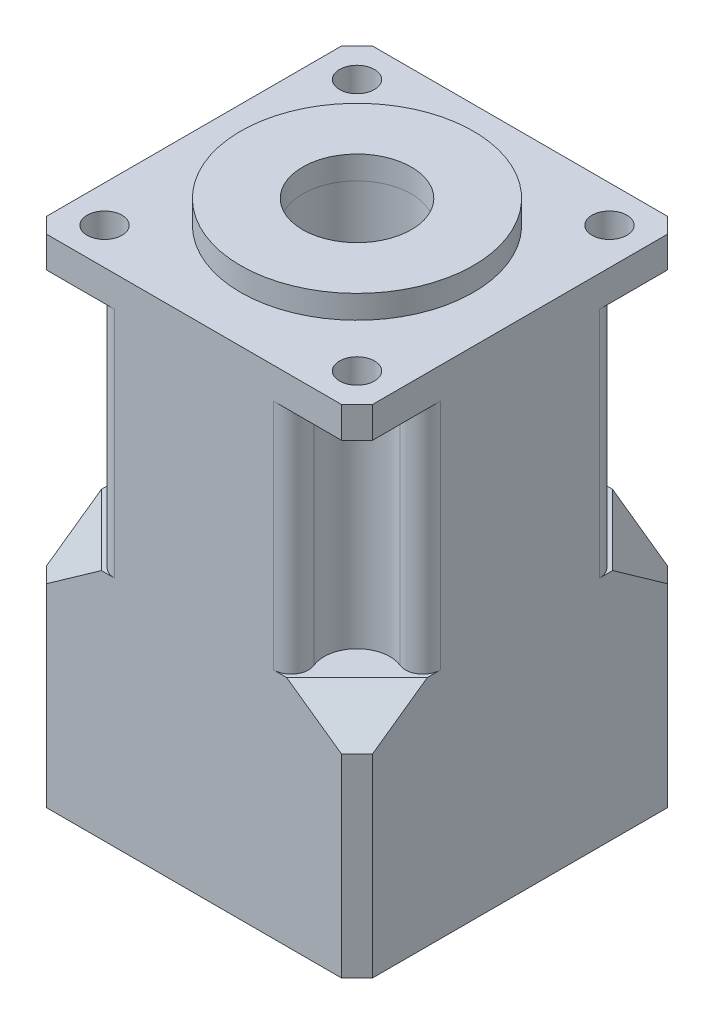
SolidWorks part; units mm, degrees
ref_plane "Front Plane" through (0, 0, 0) normal (0, 0, 1) x (1, 0, 0)
ref_plane "Top Plane" through (0, 0, 0) normal (0, 1, 0) x (1, 0, 0)
ref_plane "Right Plane" through (0, 0, 0) normal (1, 0, 0) x (0, 0, -1)
sketch "Sketch1" plane through (0, 0, 0) normal (0, 1, 0) x (1, 0, 0)
  line L0 (0, 0) -> (-23, 0) construction
  line L1 (-19, 21) -> (19, 21)
  line L2 (-21, 19) -> (-21, -19)
  line L3 (-19, -21) -> (19, -21)
  line L4 (21, 19) -> (21, -19)
  line L5 (-21, 21) -> (21, -21) construction
  line L6 (-21, -21) -> (21, 21) construction
  line L7 (-19, 21) -> (-21, 19)
  line L8 (19, 21) -> (21, 19)
  line L9 (-21, -19) -> (-19, -21)
  line L10 (19, -21) -> (21, -19)
  circle A0 centre (0, 0) radius 23 construction
  circle A1 centre (-16.2635, 16.2635) radius 2.25
  circle A3 centre (16.2635, 16.2635) radius 2.25
  circle A4 centre (16.2635, -16.2635) radius 2.25
  circle A5 centre (-16.2635, -16.2635) radius 2.25
  circle A6 centre (0, 0) radius 15
  circle A7 centre (0, 0) radius 7
  point P0 (0, 0)
  dimension "D3" = 23
  dimension "D1" = 42
  dimension "D2" = 42
extrude "Boss-Extrude1" add sketch "Sketch1" along normal blind 26 contours A7 region at (0, 0, 0)
extrude "Boss-Extrude2" add sketch "Sketch1<3>" along normal blind 3 contours A6 A7 region at (-14.5757, 0, 0)
sketch "Sketch1<3>" plane through (0, 0, 0) normal (0, 1, 0) x (1, 0, 0) same geometry as "Sketch1"
extrude "Boss-Extrude3" add sketch "Sketch1<4>" against normal blind 4 separate body contours A6 A7 | L3 L10 L4 L8 L1 L7 L2 L9 A6 A4 A3 A1 A5 | A7 region at (0, 0, -20.406) region at (-14.5757, 0, 0) region at (0, 0, 0)
sketch "Sketch1<4>" plane through (0, 0, 0) normal (0, 1, 0) x (1, 0, 0) same geometry as "Sketch1"
sketch "Sketch3" plane through (0, -4, 0) normal (0, -1, 0) x (1, 0, 0)
  line L0 (-21, -19) -> (-21, 19) construction
  line L2 (-19, 21) -> (19, 21) construction
  line L3 (21, -19) -> (21, 19) construction
  line L4 (-19, -21) -> (19, -21) construction
  line L8 (-21, 0) -> (21, 0) construction
  line L9 (-10.2579, 21) -> (10.2579, 21)
  line L10 (-21, 10.2579) -> (-21, -10.2579)
  line L11 (-10.2579, -21) -> (10.2579, -21)
  line L12 (21, 10.2579) -> (21, -10.2579)
  line L13 (0, 21) -> (0, -21) construction
  arc A0 (17.8893, 12.3367) -> (12.3367, 17.8893) centre (16.2635, 16.2635) cw
  arc A11 (12.3367, 17.8893) -> (10.2579, 21) centre (10.2579, 18.75) ccw
  arc A17 (21, 10.2579) -> (17.8893, 12.3367) centre (18.75, 10.2579) ccw
  arc A18 (-12.3367, 17.8893) -> (-10.2579, 21) centre (-10.2579, 18.75) cw
  arc A19 (-21, 10.2579) -> (-17.8893, 12.3367) centre (-18.75, 10.2579) cw
  arc A20 (-17.8893, 12.3367) -> (-12.3367, 17.8893) centre (-16.2635, 16.2635) ccw
  arc A21 (21, -10.2579) -> (17.8893, -12.3367) centre (18.75, -10.2579) cw
  arc A22 (17.8893, -12.3367) -> (12.3367, -17.8893) centre (16.2635, -16.2635) ccw
  arc A23 (12.3367, -17.8893) -> (10.2579, -21) centre (10.2579, -18.75) cw
  arc A24 (-21, -10.2579) -> (-17.8893, -12.3367) centre (-18.75, -10.2579) ccw
  arc A25 (-17.8893, -12.3367) -> (-12.3367, -17.8893) centre (-16.2635, -16.2635) cw
  arc A26 (-12.3367, -17.8893) -> (-10.2579, -21) centre (-10.2579, -18.75) ccw
  dimension "D1" = 4.5
extrude "Boss-Extrude4" add sketch "Sketch3" along normal blind 30
extrude "Boss-Extrude6" add sketch "Sketch1<6>" against normal blind 30 from surface contours L3 L10 L4 L8 L1 L7 L2 L9 A6 A4 A3 A1 A5 | A1 | A3 | A4 | A5 | A6 A7 region at (0, 0, -20.406) region at (-16.2635, 0, -16.2635) region at (16.2635, 0, -16.2635) region at (16.2635, 0, 16.2635) region at (-16.2635, 0, 16.2635) region at (-14.5757, 0, 0) starting at face at (0, -34, 0)
sketch "Sketch1<6>" plane through (0, 0, 0) normal (0, 1, 0) x (1, 0, 0) same geometry as "Sketch1"
extrude "Cut-Extrude3" cut sketch "Sketch1<7>" along normal blind 5 from surface contours A5 | A1 | A3 | A4 region at (-16.2635, 0, -16.2635) region at (16.2635, 0, -16.2635) region at (16.2635, 0, 16.2635) region at (-16.2635, 0, 16.2635) starting at face at (0, -64, 0)
sketch "Sketch1<7>" plane through (0, 0, 0) normal (0, 1, 0) x (1, 0, 0) same geometry as "Sketch1"
extrude "Cut-Extrude4" cut sketch "Sketch1<8>" along normal blind 5 from surface contours A6 A7 region at (-14.5757, 0, 0) starting at face at (16.2635, -64, 18.5135)
sketch "Sketch1<8>" plane through (0, 0, 0) normal (0, 1, 0) x (1, 0, 0) same geometry as "Sketch1"
fillet "Chamfer1" radius 5 1 edges at (-20, -34, -20) type face fillet profile chamfer first side face at (-16.836, -34, -16.836) second side face at (-20, -49, -20)
fillet "Chamfer2" radius 5 1 edges at (20, -34, -20) type face fillet profile chamfer first side face at (16.836, -34, -16.836) second side face at (20, -49, -20)
fillet "Chamfer3" radius 5 1 edges at (-20, -34, 20) type face fillet profile chamfer first side face at (-16.836, -34, 16.836) second side face at (-20, -49, 20)
fillet "Chamfer4" radius 5 1 edges at (20, -34, 20) type face fillet profile chamfer first side face at (16.836, -34, 16.836) second side face at (20, -49, 20)
sketch "Sketch4" plane through (0, 26, 0) normal (0, 1, 0) x (1, 0, 0)
  circle A0 centre (0, 0) radius 7
extrude "Cut-Extrude5" cut sketch "Sketch4" against normal up to surface (85 mm away) up to face at (0, -59, 15)
